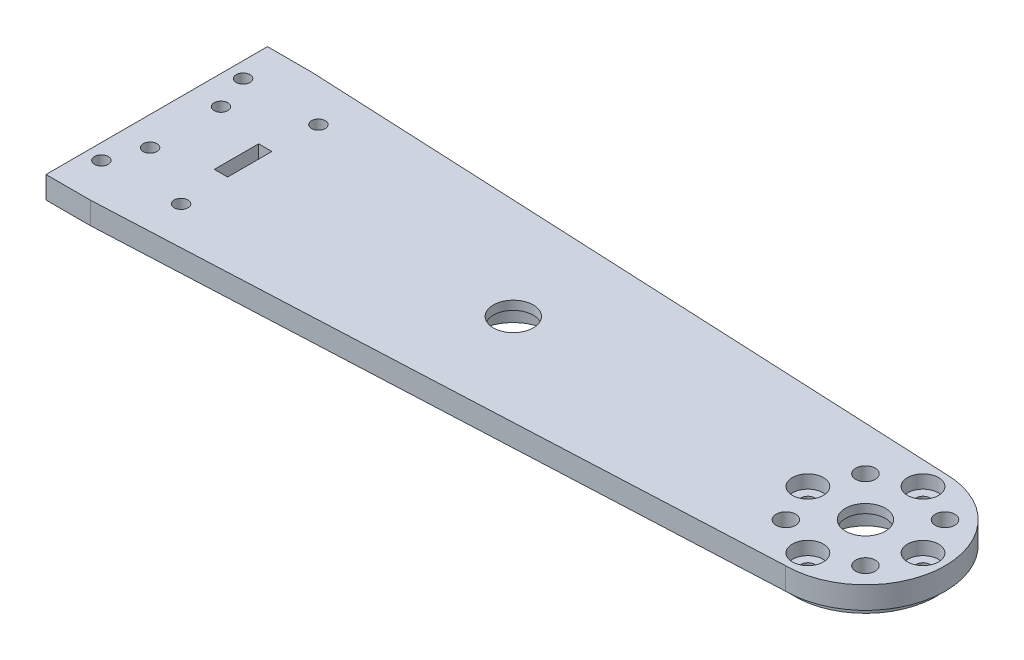
SolidWorks part; units mm, degrees
ref_plane "Front Plane" through (0, 0, 0) normal (0, 0, 1) x (1, 0, 0)
ref_plane "Top Plane" through (0, 0, 0) normal (0, 1, 0) x (1, 0, 0)
ref_plane "Right Plane" through (0, 0, 0) normal (1, 0, 0) x (0, 0, -1)
sketch "Sketch28" plane through (-32, 0, 0) normal (0, -1, 0) x (0, 0, 1)
  line L1 (0, -20) -> (0, -65.5) construction
  line L2 (-8, 8.5) -> (8, 8.5) construction
  line L3 (0, 15) -> (0, -3) construction
  line L8 (-25, 15) -> (25, 15)
  line L12 (25, 15) -> (25, 5)
  line L13 (-25, 15) -> (-25, 5)
  line L14 (-25, 5) -> (-18, -145)
  line L15 (18, -145) -> (25, 5)
  line L16 (-25, 5) -> (-25, 8.5) construction
  line L17 (-25, 8.5) -> (-8, 8.5) construction
  line L18 (-25, 15) -> (-25, 11.5) construction
  line L19 (-25, 11.5) -> (-16, 11.5) construction
  line L20 (-16, 11.5) -> (16, 11.5) construction
  line L21 (-5, -3) -> (5, -3)
  line L26 (5, -3) -> (5, -6)
  line L27 (5, -6) -> (-5, -6)
  line L28 (-5, -6) -> (-5, -3)
  line L29 (-5, -3) -> (-15.5, -3) construction
  line L30 (-15.5, -3) -> (-15.5, -6) construction
  line L31 (5, -3) -> (15.5, -3) construction
  line L32 (15.5, -3) -> (15.5, -6) construction
  line L33 (0, -20) -> (0, -6) construction
  line L34 (0, -65.5) -> (0, -145) construction
  circle A7 centre (8, 8.5) radius 1.55
  circle A8 centre (-8, 8.5) radius 1.55
  circle A9 centre (16, 11.5) radius 1.55
  circle A10 centre (-16, 11.5) radius 1.55
  circle A13 centre (-15.5, -6) radius 1.55
  circle A14 centre (15.5, -6) radius 1.55
  circle A15 centre (0, -20) radius 12.5 construction
  arc A17 (-18, -145) -> (18, -145) centre (0, -145) ccw
  circle A19 centre (0, -145) radius 4.5
  circle A20 centre (0, -65.5) radius 4.5
  point P13 (0, 15)
  point P27 (0, -3)
extrude "Boss-Extrude10" add sketch "Sketch28" along normal blind 5
sketch "Sketch29" plane through (0, -5, 0) normal (0, -1, 0) x (1, 0, 0)
  circle A0 centre (113, 0) radius 16
  circle A2 centre (33.5, 0) radius 16
extrude "Boss-Extrude11" add sketch "Sketch29" along normal blind 2
sketch "Sketch30" plane through (0, -7, 0) normal (0, -1, 0) x (1, 0, 0)
  circle A0 centre (33.5, 0) radius 8.2
  circle A1 centre (113, 0) radius 8.2
extrude "Cut-Extrude1" cut sketch "Sketch30" against normal blind 5
sketch "Sketch31" plane through (0, -7, 0) normal (0, -1, 0) x (1, 0, 0)
  line L0 (113, 0) -> (121.9803, 8.9803) construction
  circle A0 centre (113, 0) radius 12.7 construction
  circle A1 centre (121.9803, 8.9803) radius 1.2
  circle A2 centre (121.9803, -8.9803) radius 1.2
  circle A3 centre (104.0197, -8.9803) radius 1.2
  circle A4 centre (104.0197, 8.9803) radius 1.2
  circle A5 centre (113, 0) radius 13 construction
  circle A6 centre (113, 13) radius 1.55
  circle A7 centre (126, 0) radius 1.55
  circle A8 centre (113, -13) radius 1.55
  circle A9 centre (100, 0) radius 1.55
  point P14 (113, 0)
  point P15 (113, 0)
  point P24 (113, 0)
  dimension "D1" = 4
  dimension "D2" = 4
extrude "Cut-Extrude2" cut sketch "Sketch31" against normal up to surface (7 mm away) up to face at (-43.5, 0, -17.55)
sketch "Sketch32" plane through (0, 0, 0) normal (0, 1, 0) x (1, 0, 0)
  circle A0 centre (113, 13) radius 3.5
  circle A1 centre (100, 0) radius 3.5
  circle A2 centre (113, -13) radius 3.5
  circle A3 centre (126, 0) radius 3.5
  point P12 (113, 0)
  point P22 (33.5, 0)
  dimension "D1" = 4
extrude "Cut-Extrude3" cut sketch "Sketch32" against normal blind 3
sketch "Sketch33" plane through (0, 0, 0) normal (0, 1, 0) x (1, 0, 0)
  circle A0 centre (104.0197, 8.9803) radius 2.2
  circle A1 centre (121.9803, 8.9803) radius 2.2
  circle A2 centre (121.9803, -8.9803) radius 2.2
  circle A3 centre (104.0197, -8.9803) radius 2.2
  point P12 (113, 0)
extrude "Cut-Extrude4" cut sketch "Sketch33" against normal blind 5
